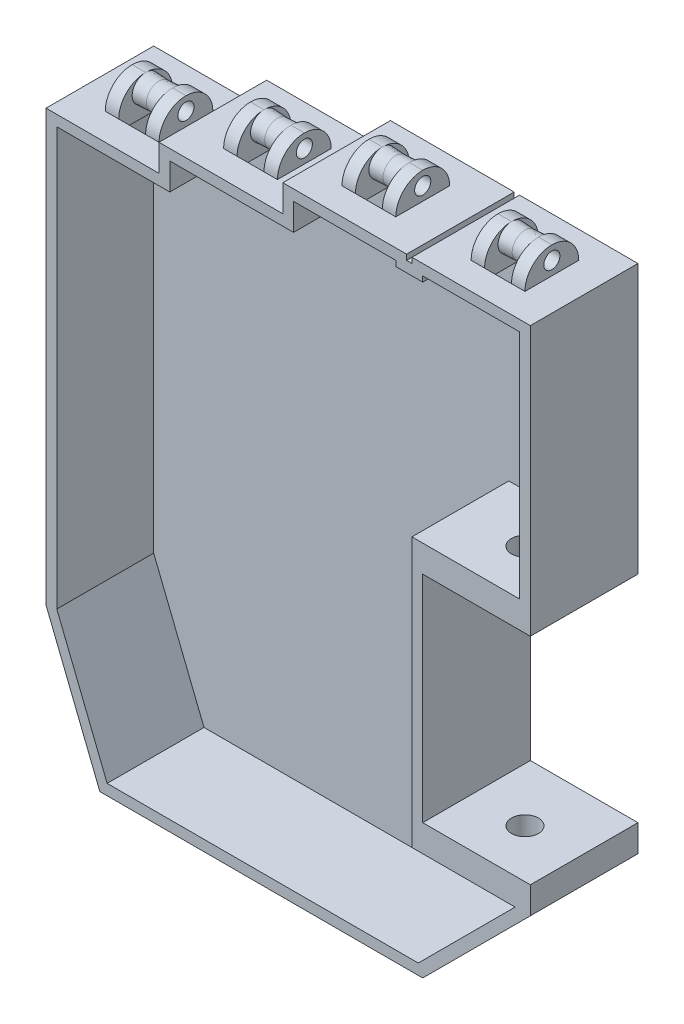
SolidWorks part; units mm, degrees
ref_plane "Front Plane" through (0, 0, 0) normal (0, 0, 1) x (1, 0, 0)
ref_plane "Top Plane" through (0, 0, 0) normal (0, 1, 0) x (1, 0, 0)
ref_plane "Right Plane" through (0, 0, 0) normal (1, 0, 0) x (0, 0, -1)
sketch "Sketch1" plane through (0, 0, 0) normal (0, 0, 1) x (1, 0, 0)
  line L0 (0, 0) -> (60, 0)
  line L1 (60, 0) -> (80, 20)
  line L2 (80, 20) -> (80, 115)
  line L3 (80, 115) -> (58, 115)
  line L4 (-10, 105) -> (11, 105)
  line L5 (-10, 105) -> (-10, 25)
  line L6 (-10, 25) -> (0, 0)
  line L7 (57, 115) -> (57, 114)
  line L8 (35, 115) -> (57, 115)
  line L9 (34, 115) -> (34, 110)
  line L10 (35, 115) -> (34, 115)
  line L11 (34, 110) -> (12, 110)
  line L12 (12, 110) -> (11, 110)
  line L13 (11, 110) -> (11, 105)
  line L14 (57, 115) -> (58, 115)
  line L15 (57, 114) -> (58, 114)
  line L16 (58, 114) -> (58, 115)
  dimension "D1" = 60
  dimension "D2" = 22
  dimension "D3" = 90
  dimension "D4" = 20
  dimension "D5" = 80
  dimension "D6" = 95
  dimension "D7" = 135
  dimension "D8" = 1
  dimension "D9" = 22
  dimension "D10" = 22
  dimension "D11" = 1
  dimension "D12" = 5
  dimension "D13" = 1
  dimension "D14" = 5
  dimension "D15" = 1
extrude "Boss-Extrude1" add sketch "Sketch1" along normal blind 20 contours L16 L15 L7 L8 L10 L9 L11 L12 L13 L4 L5 L6 L0 L1 L2 L3 region at (35.6394, 57.3872, 0)
sketch "Sketch2" plane through (0, 0, 20) normal (0, 0, 1) x (1, 0, 0)
  line L0 (80, 25) -> (60, 25)
  line L2 (60, 25) -> (60, 65)
  line L3 (60, 65) -> (80, 65)
  line L4 (80, 65) -> (80, 25)
  dimension "D1" = 20
  dimension "D2" = 5
  dimension "D3" = 40
extrude "Cut-Extrude1" cut sketch "Sketch2" against normal through all
shell "Shell1" thickness 2 removed face at (44.4444, 74.6111, 20)
sketch "Sketch34" plane through (0, 70, 0) normal (0, 1, 0) x (1, 0, 0)
  line L0 (58, -2) -> (58, -20) construction
  line L1 (78, -2) -> (58, -2) construction
  circle A0 centre (70, -11) radius 2.5
  dimension "D3" = 5
  dimension "D1" = 12
  dimension "D2" = 9
extrude "Cut-Extrude14" cut sketch "Sketch34" against normal up to surface (50 mm away) up to face at (67.5858, 20, 11)
sketch "Sketch3" plane through (0, 115, 0) normal (0, 1, 0) x (1, 0, 0)
  line L2 (74, -5) -> (64, -5)
  line L3 (74, -5) -> (74, -15)
  line L4 (74, -15) -> (64, -15)
  line L5 (64, -5) -> (64, -15)
  line L6 (74, -5) -> (64, -15) construction
  line L7 (74, -15) -> (64, -5) construction
  line L8 (66.5, -5) -> (66.5, -15)
  line L9 (71.5, -5) -> (71.5, -15)
  point P0 (69, -10)
  dimension "D1" = 10
  dimension "D2" = 10
  dimension "D3" = 5
  dimension "D4" = 2.5
extrude "Boss-Extrude2" add sketch "Sketch3" along normal blind 5 contours L8 L2 L5 L4 | L2 L9 L4 L3 region at (72.75, 115, 10) region at (65.25, 115, 10)
fillet "Fillet2" radius 5 4 edges at (65.25, 120, 5) (65.25, 120, 15) (72.75, 120, 5) (72.75, 120, 15)
sketch "Sketch6" plane through (74, 0, 0) normal (1, 0, 0) x (0, 0, -1)
  circle A0 centre (-10, 117.5) radius 1.5
  dimension "D1" = 3
  dimension "D2" = 2.5
extrude "Cut-Extrude3" cut sketch "Sketch6" against normal up to surface (10 mm away) up to face at (64, 117.357, 10)
sketch "Sketch21" plane through (66.5, 0, 0) normal (1, 0, 0) x (0, 0, -1)
  circle A0 centre (-10, 117.5) radius 1.5
  circle A1 centre (-10, 117.5) radius 2.5
  circle M1 centre (-10, 117.5) radius 1.5
  dimension "D1" = 5
extrude "Boss-Extrude10" add sketch "Sketch21" along normal blind 2.5 draft 3 contours A1 M1 region at (66.5, 117.5, 12.4293)
mirror "Mirror7" about plane through (69, 0, 0) normal (1, 0, 0) of "Boss-Extrude10"
sketch "Sketch26" plane through (0, 115, 0) normal (0, 1, 0) x (1, 0, 0)
  line L1 (66.5, -15) -> (71.5, -15)
  line L2 (66.5, -15) -> (66.5, -5)
  line L3 (66.5, -5) -> (71.5, -5)
  line L4 (71.5, -15) -> (71.5, -5)
  dimension "D1" = 5
  dimension "D2" = 10
extrude "Cut-Extrude8" cut sketch "Sketch26" against normal up to surface (2 mm away) up to face at (69, 113, 11)
sketch "Sketch7" plane through (0, 115, 0) normal (0, 1, 0) x (1, 0, 0)
  line L0 (50, -5) -> (40, -5)
  line L1 (50, -5) -> (50, -15)
  line L2 (50, -15) -> (40, -15)
  line L3 (40, -5) -> (40, -15)
  line L4 (50, -5) -> (40, -15) construction
  line L5 (50, -15) -> (40, -5) construction
  line L6 (42.5, -5) -> (42.5, -15)
  line L7 (47.5, -5) -> (47.5, -15)
  line L9 (34, -20) -> (34, 0) construction
  point P0 (45, -10)
  point P11 (34, -10)
  dimension "D1" = 10
  dimension "D2" = 10
  dimension "D3" = 5
  dimension "D4" = 2.5
extrude "Boss-Extrude4" add sketch "Sketch7" along normal blind 5 contours L6 L0 L3 L2 | L0 L7 L2 L1 region at (48.75, 115, 10) region at (41.25, 115, 10)
fillet "Fillet4" radius 5 4 edges at (41.25, 120, 5) (41.25, 120, 15) (48.75, 120, 5) (48.75, 120, 15)
sketch "Sketch22" plane through (42.5, 0, 0) normal (1, 0, 0) x (0, 0, -1)
  circle A0 centre (-10, 117.5) radius 2.5
  dimension "D1" = 5
  dimension "D2" = 2.5
  dimension "D3" = 0
extrude "Boss-Extrude11" add sketch "Sketch22" along normal blind 2.5 draft 3
mirror "Mirror8" about plane through (45, 117.5, 10) normal (1, 0, 0) of "Boss-Extrude11"
sketch "Sketch23" plane through (50, 0, 0) normal (1, 0, 0) x (0, 0, -1)
  circle A0 centre (-10, 117.5) radius 1.5
  dimension "D3" = 3
  dimension "D1" = 0
  dimension "D2" = 2.5
extrude "Cut-Extrude7" cut sketch "Sketch23" against normal up to surface (10 mm away) up to face at (40, 117.357, 10)
sketch "Sketch27" plane through (0, 115, 0) normal (0, 1, 0) x (1, 0, 0)
  line L1 (42.5, -15) -> (47.5, -15)
  line L2 (42.5, -15) -> (42.5, -5)
  line L3 (42.5, -5) -> (47.5, -5)
  line L4 (47.5, -15) -> (47.5, -5)
  dimension "D1" = 5
  dimension "D2" = 10
extrude "Cut-Extrude9" cut sketch "Sketch27" against normal up to surface (2 mm away) up to face at (45.5, 113, 11)
sketch "Sketch10" plane through (0, 110, 0) normal (0, 1, 0) x (1, 0, 0)
  line L0 (28, -5) -> (18, -5)
  line L1 (28, -5) -> (28, -15)
  line L2 (28, -15) -> (18, -15)
  line L3 (18, -5) -> (18, -15)
  line L4 (28, -5) -> (18, -15) construction
  line L5 (28, -15) -> (18, -5) construction
  line L6 (20.5, -5) -> (20.5, -15)
  line L7 (25.5, -5) -> (25.5, -15)
  line L8 (34, 0) -> (11, 0) construction
  line L10 (34, -20) -> (34, 0) construction
  point P0 (23, -10)
  point P11 (22.5, 0)
  dimension "D1" = 10
  dimension "D2" = 10
  dimension "D3" = 5
  dimension "D4" = 2.5
  dimension "D5" = 10
  dimension "D6" = 11
extrude "Boss-Extrude6" add sketch "Sketch10" along normal blind 5 contours L6 L0 L3 L2 | L0 L7 L2 L1 region at (26.75, 110, 10) region at (19.25, 110, 10)
fillet "Fillet6" radius 5 4 edges at (19.25, 115, 15) (19.25, 115, 5) (26.75, 115, 5) (26.75, 115, 15)
sketch "Sketch28" plane through (20.5, 0, 0) normal (1, 0, 0) x (0, 0, -1)
  circle A0 centre (-10, 112.5) radius 2.5
  dimension "D3" = 5
  dimension "D1" = 2.5
  dimension "D2" = 0
extrude "Boss-Extrude12" add sketch "Sketch28" along normal blind 2.5 draft 3
mirror "Mirror9" about plane through (23, 112.5, 10) normal (1, 0, 0) of "Boss-Extrude12"
sketch "Sketch29" plane through (28, 0, 0) normal (1, 0, 0) x (0, 0, -1)
  circle A0 centre (-10, 112.5) radius 1.5
  dimension "D3" = 3
  dimension "D1" = 2.5
  dimension "D2" = 0
extrude "Cut-Extrude10" cut sketch "Sketch29" against normal up to surface (10 mm away) up to face at (18, 112.357, 10)
sketch "Sketch30" plane through (0, 110, 0) normal (0, 1, 0) x (1, 0, 0)
  line L1 (20.5, -15) -> (25.5, -15)
  line L2 (20.5, -15) -> (20.5, -5)
  line L3 (20.5, -5) -> (25.5, -5)
  line L4 (25.5, -15) -> (25.5, -5)
  dimension "D1" = 5
  dimension "D2" = 10
extrude "Cut-Extrude11" cut sketch "Sketch30" against normal up to surface (2 mm away) up to face at (24.5, 108, 11)
sketch "Sketch13" plane through (0, 105, 0) normal (0, 1, 0) x (1, 0, 0)
  line L0 (6, -5) -> (-4, -5)
  line L1 (6, -5) -> (6, -15)
  line L2 (6, -15) -> (-4, -15)
  line L3 (-4, -5) -> (-4, -15)
  line L4 (6, -5) -> (-4, -15) construction
  line L5 (6, -15) -> (-4, -5) construction
  line L6 (-1.5, -5) -> (-1.5, -15)
  line L7 (3.5, -5) -> (3.5, -15)
  line L8 (-10, 0) -> (11, 0) construction
  line L9 (-10, -20) -> (-10, 0) construction
  point P0 (1, -10)
  dimension "D1" = 10
  dimension "D2" = 10
  dimension "D3" = 5
  dimension "D4" = 2.5
  dimension "D5" = 10
  dimension "D6" = 11
extrude "Boss-Extrude8" add sketch "Sketch13" along normal blind 5 contours L6 L0 L3 L2 | L0 L7 L2 L1 region at (4.75, 105, 10) region at (-2.75, 105, 10)
fillet "Fillet8" radius 5 4 edges at (-2.75, 110, 15) (-2.75, 110, 5) (4.75, 110, 5) (4.75, 110, 15)
sketch "Sketch31" plane through (-1.5, 0, 0) normal (1, 0, 0) x (0, 0, -1)
  circle A0 centre (-10, 107.5) radius 2.5
  dimension "D3" = 5
  dimension "D1" = 2.5
  dimension "D2" = 0
extrude "Boss-Extrude13" add sketch "Sketch31" along normal blind 2.5 draft 3
mirror "Mirror10" about plane through (1, 107.5, 10) normal (1, 0, 0) of "Boss-Extrude13"
sketch "Sketch32" plane through (6, 0, 0) normal (1, 0, 0) x (0, 0, -1)
  circle A0 centre (-10, 107.5) radius 1.5
  dimension "D2" = 3
  dimension "D1" = 2.5
extrude "Cut-Extrude12" cut sketch "Sketch32" against normal up to surface (10 mm away) up to face at (-4, 107.357, 10)
sketch "Sketch33" plane through (0, 105, 0) normal (0, 1, 0) x (1, 0, 0)
  line L1 (-1.5, -5) -> (3.5, -5)
  line L2 (-1.5, -5) -> (-1.5, -15)
  line L3 (-1.5, -15) -> (3.5, -15)
  line L4 (3.5, -5) -> (3.5, -15)
  dimension "D1" = 5
  dimension "D2" = 10
extrude "Cut-Extrude13" cut sketch "Sketch33" against normal up to surface (2 mm away) up to face at (2.5, 103, 11)
sketch "Sketch37" plane through (78, 0, 0) normal (-1, 0, 0) x (0, 0, 1)
  line L0 (2, 105) -> (13, 105)
  line L1 (2, 70) -> (2, 113) construction
  line L2 (20, 113) -> (2, 113) construction
  dimension "D1" = 8
  dimension "D2" = 11
